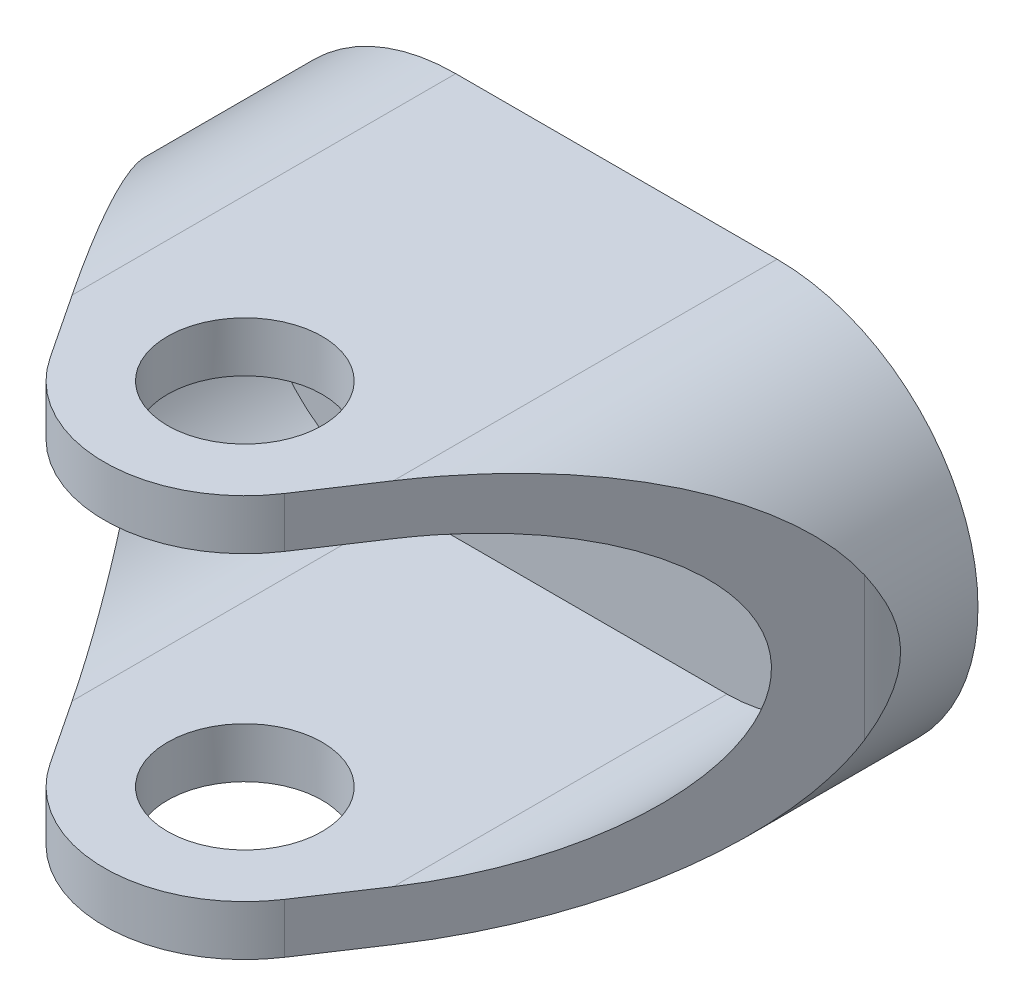
SolidWorks part; units mm, degrees
material "6061 Alloy"
ref_plane "Front Plane" through (0, 0, 0) normal (0, 0, 1) x (1, 0, 0)
ref_plane "Top Plane" through (0, 0, 0) normal (0, 1, 0) x (1, 0, 0)
ref_plane "Right Plane" through (0, 0, 0) normal (1, 0, 0) x (0, 0, -1)
sketch "Sketch1" plane through (0, 0, 0) normal (0, 1, 0) x (1, 0, 0)
  line L0 (-24.13, -19.05) -> (24.13, -19.05)
  line L1 (-24.13, -19.05) -> (-24.13, 19.05)
  line L2 (24.13, -19.05) -> (24.13, 19.05)
  line L3 (-24.13, 19.05) -> (24.13, 19.05)
  line L4 (-24.13, -19.05) -> (24.13, 19.05) construction
  line L5 (24.13, -19.05) -> (-24.13, 19.05) construction
  point P1 (0, 0)
  dimension "D1" = 38.1
  dimension "D2" = 48.26
extrude "Billet" add sketch "Sketch1" along normal blind 25.4
sketch "Sketch2" plane through (0, 25.4, 0) normal (0, 1, 0) x (1, 0, 0)
  line L1 (-7.4106, -9.3557) -> (-24.13, 15.875)
  line L3 (24.13, 19.05) -> (-24.13, 19.05) construction
  line L4 (-24.13, 15.875) -> (24.13, 15.875) construction
  line L5 (0, -14.605) -> (0, -11.9174) construction
  line L6 (-24.13, 15.875) -> (-24.13, -19.05)
  line L7 (-24.13, -19.05) -> (24.13, -19.05)
  line L8 (24.13, -19.05) -> (24.13, 15.875)
  line L9 (7.4106, -9.3557) -> (24.13, 15.875)
  arc A0 (7.4106, -9.3557) -> (-7.4106, -9.3557) centre (0, -4.445) cw
  circle A1 centre (0, -4.445) radius 4.8895
  line M1 (-24.13, 19.05) -> (-24.13, -19.05)
  line M2 (-24.13, -19.05) -> (24.13, -19.05)
  line M3 (24.13, -19.05) -> (24.13, 19.05)
  dimension "D1" = 8.89
  dimension "D3" = 9.779
  dimension "D2" = 3.175
  dimension "D4" = 20.32
extrude "Mill Cut 1" cut sketch "Sketch2" against normal through all contours L9 A0 L1 M1 M2 M3 | A1 region at (0, 25.4, 13.9307) region at (0, 25.4, 4.445)
fillet "Fillet2" radius 12.7 2 edges at (-24.13, 12.7, -15.875) (24.13, 12.7, -15.875)
fillet "Fillet1" [suppressed] radius 1.27
ref_plane "Plane2" through (0, 25.4, 13.335) normal (0, 0, 1) x (1, 0, 0)
sketch "Sketch6" plane through (0, 25.4, 13.335) normal (0, 0, 1) x (1, 0, 0)
  line L0 (7.4106, 0) -> (-7.4106, 0) construction
  line L1 (-10.16, -3.175) -> (10.16, -3.175)
  line L2 (-10.16, -3.175) -> (-10.16, -22.225)
  line L3 (-10.16, -22.225) -> (10.16, -22.225)
  line L4 (10.16, -3.175) -> (10.16, -22.225)
  line L5 (0, -3.175) -> (0, 0) construction
  line L6 (0, -22.225) -> (0, -25.4) construction
  line L7 (-24.13, 0) -> (-24.13, -25.4) construction
  arc A0 (-10.16, -3.175) -> (-10.16, -22.225) centre (-10.16, -12.7) ccw
  arc A1 (10.16, -3.175) -> (10.16, -22.225) centre (10.16, -12.7) cw
  point P6 (0, 0)
  point P7 (0, -3.175)
  dimension "D1" = 3.175
  dimension "D2" = 13.97
extrude "Cut-Extrude1" cut sketch "Sketch6" against normal offset from surface (29.21 mm away) 3.175 contours L2 | L4 L1 L2 L3 | L4 region at (0, 12.7, 13.335) region at (-14.2025, 12.7, 13.335) region at (14.2025, 12.7, 13.335) up to face at (0, 12.7, -19.05)
sketch "Sketch8" plane through (0, 25.4, 13.335) normal (0, 0, 1) x (1, 0, 0)
  line L7 (-7.4106, 0) -> (-22.0347, 0) construction
  line L8 (-10.16, -25.4) -> (-60.96, -25.4)
  line L9 (-60.96, -25.4) -> (-60.96, 0)
  line L10 (-60.96, 0) -> (-10.16, 0)
  line L11 (-7.4106, -25.4) -> (-22.0347, -25.4) construction
  arc A4 (-10.16, 0) -> (-10.16, -25.4) centre (-10.16, -12.7) ccw
  arc A8 (-10.16, -3.175) -> (-10.16, -22.225) centre (-10.16, -12.7) ccw construction
  dimension "D1" = 50.8
extrude "Cut-Extrude2" cut sketch "Sketch8" against normal through all
mirror "Mirror1" about plane through (0, 0, 0) normal (1, 0, 0) of "Cut-Extrude2"
sketch "Sketch9" plane through (0, 0, -15.875) normal (0, 0, 1) x (1, 0, 0)
  line L0 (0, 25.4) -> (0, 0) construction
  line L1 (7.4106, 25.4) -> (-7.4106, 25.4) construction
  line L2 (0, 12.7) -> (12.7, 12.7) construction
  circle A0 centre (12.7, 12.7) radius 3.175
  circle A1 centre (-12.7, 12.7) radius 3.175
  dimension "D1" = 6.35
  dimension "D2" = 12.7
extrude "Holes" cut sketch "Sketch9" against normal through all
ref_axis "Axis1" [suppressed] through (0, 22.225, 4.445) along (0, 1, 0)
ref_plane "Plane1" [suppressed] through (1.4286, 0, 0.52) normal (-0.9397, 0, -0.342) x (0, 1, 0)
sketch "Sketch5" [suppressed] plane through (0, 25.4, 0) normal (0, 1, 0) x (1, 0, 0)
  circle A0 centre (0, -4.445) radius 4.8895
extrude "Mock Bolt" [suppressed] add sketch "Sketch5" against normal through all
